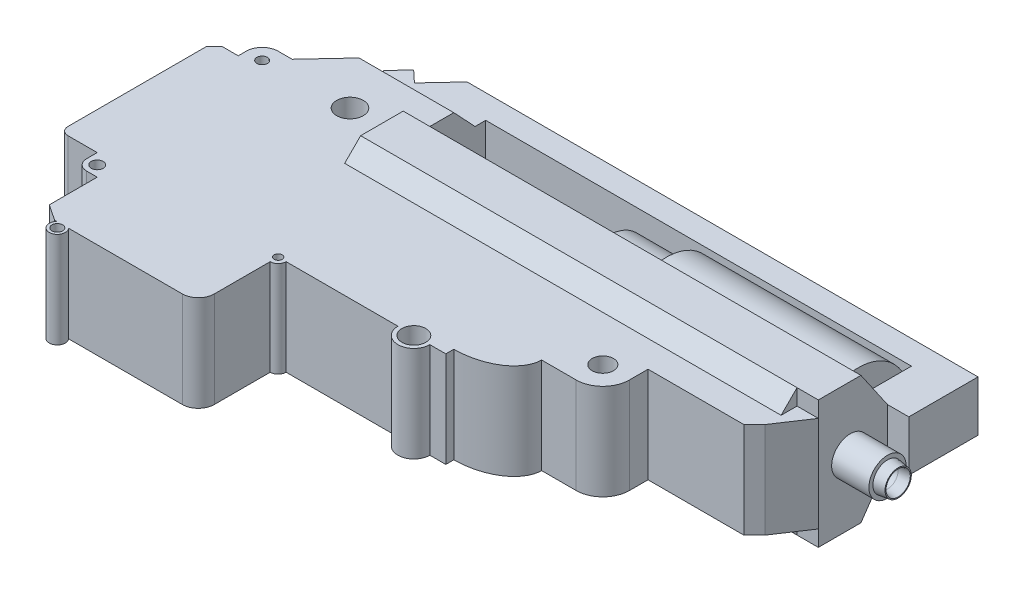
SolidWorks part; units mm, degrees
ref_plane "Alzado" through (0, 0, 0) normal (0, 0, 1) x (1, 0, 0)
ref_plane "Planta" through (0, 0, 0) normal (0, 1, 0) x (1, 0, 0)
ref_plane "Vista lateral" through (0, 0, 0) normal (1, 0, 0) x (0, 0, -1)
sketch "Croquis1" plane through (0, 0, 0) normal (0, 1, 0) x (1, 0, 0)
  line L0 (0, 0) -> (96, 0)
  line L1 (96, 0) -> (96, -13)
  line L2 (0, 0) -> (-4.2707, -4.5758)
  line L3 (96, -13) -> (88, -13)
  line L4 (96, -13) -> (96, -10.5)
  line L6 (88, -4.5) -> (88, -13)
  line L7 (88, -4.5) -> (8, -4.5)
  line L8 (88, -13) -> (87.902, -13.0151)
  line L9 (8, -4.5) -> (8, -7.5)
  line L10 (8, -7.5) -> (-7, -7.5)
  line L11 (-7, -7.5) -> (-9.9242, -4.7707)
  line L12 (-9.9242, -4.7707) -> (-7.1949, -1.8465)
  line L13 (-7.1949, -1.8465) -> (-4.2707, -4.5758)
  line L14 (-7, -7.5) -> (-10.4116, -11.1553) construction
  line L15 (-13.3358, -8.426) -> (-10.4116, -11.1553)
  line L16 (-13.1409, -14.0795) -> (-16.0651, -11.3502)
  line L17 (-16.0651, -11.3502) -> (-13.3358, -8.426)
  line L18 (-13.1409, -14.0795) -> (-10.4116, -11.1553)
  dimension "D1" = 96
  dimension "D2" = 13
  dimension "D3" = 15
  dimension "D4" = 8
  dimension "D8" = 80
  dimension "D9" = 4
  dimension "D10" = 4
  dimension "D11" = 5
extrude "Saliente-Extruir1" add sketch "Croquis1" along normal blind 9.5 contours L1 L0 L2 L10 L9 L7 L6 L3 | L16 L18 L15 L17 region at (47.5288, 0, 3.3855) region at (-13.2383, 0, 11.2528)
sketch "Croquis2" plane through (88, 0, 0) normal (-1, 0, 0) x (0, 0, 1)
  line L0 (4.5, 4.75) -> (5, 4.75) construction
  line L2 (4.5, 9.5) -> (4.5, 0) construction
  line L3 (5, 4.75) -> (14.5, 4.75) construction
  circle A0 centre (14.5, 4.75) radius 9.5
  dimension "D1" = 0.5
  dimension "D2" = 9.5
extrude "Saliente-Extruir2" add sketch "Croquis2" along normal blind 36
sketch "Croquis3" plane through (52, 0, 0) normal (-1, 0, 0) x (0, 0, 1)
  circle A0 centre (14.5, 4.75) radius 7.5
  dimension "D1" = 15
extrude "Saliente-Extruir3" add sketch "Croquis3" along normal blind 11
sketch "Croquis5" plane through (41, 0, 0) normal (-1, 0, 0) x (0, 0, 1)
  circle A0 centre (14.5, 4.75) radius 3.5
  dimension "D1" = 7
extrude "Saliente-Extruir4" add sketch "Croquis5" along normal blind 33
sketch "Croquis6" plane through (88, 0, 0) normal (1, 0, 0) x (0, 0, -1)
  line L0 (-13, 4.75) -> (-26, 4.75) construction
  line L1 (-13, 9.5) -> (-13, 0) construction
  line L2 (-26, -7.25) -> (-26, 16.75)
  line L3 (-26, 16.75) -> (-18, 16.75)
  line L4 (-18, 16.75) -> (-13, 9.5)
  line L5 (-13, 9.5) -> (-13, 0)
  line L6 (-18, -7.25) -> (-13, 0)
  line L7 (-26, -7.25) -> (-18, -7.25)
  dimension "D1" = 13
  dimension "D2" = 12
  dimension "D3" = 8
extrude "Saliente-Extruir5" add sketch "Croquis6" along normal blind 4
sketch "Croquis7" plane through (92, 0, 0) normal (1, 0, 0) x (0, 0, -1)
  line L0 (-13, 4.75) -> (-20, 4.75) construction
  line L1 (-13, 0) -> (-13, 9.5) construction
  circle A0 centre (-20, 4.75) radius 3.5
  circle A1 centre (-20, 4.75) radius 2
  dimension "D2" = 7
  dimension "D3" = 4
  dimension "D1" = 7
extrude "Saliente-Extruir6" add sketch "Croquis7" along normal blind 7
sketch "Croquis8" plane through (99, 0, 0) normal (1, 0, 0) x (0, 0, -1)
  circle A0 centre (-20, 4.75) radius 2
  circle A1 centre (-20, 4.75) radius 2.75
  dimension "D1" = 5.5
extrude "Saliente-Extruir7" add sketch "Croquis8" along normal blind 2 draft 8
sketch "Croquis9" plane through (8, 0, 0) normal (-1, 0, 0) x (0, 0, 1)
  line L10 (6.5, 9.5) -> (10.5, 13.75)
  line L13 (4.5, 4.75) -> (17.5, 4.75) construction
  line L14 (10.5, 13.75) -> (17.5, 13.75)
  line L15 (17.5, -4.25) -> (17.5, 13.75)
  line L18 (4.5, 0) -> (4.5, 9.5)
  line L19 (4.5, 0) -> (6.5, 0)
  line L20 (4.5, 9.5) -> (10.5, 9.5) construction
  line L21 (17.5, -4.25) -> (10.5, -4.25)
  line L22 (4.5, 9.5) -> (6.5, 9.5)
  line L23 (10.5, 9.5) -> (10.5, 13.75) construction
  line L24 (6.5, 0) -> (10.5, -4.25)
  dimension "D3" = 13
  dimension "D6" = 2
  dimension "D7" = 6
extrude "Saliente-Extruir8" add sketch "Croquis9" along normal blind 23
sketch "Croquis17" plane through (0, 13.75, 0) normal (0, 1, 0) x (1, 0, 0)
  line L0 (0, 0) -> (-16.8, -18)
  line L1 (-16.8, -18) -> (-16.7852, -17.9144)
  line L4 (0, 0) -> (-16.8, 0)
  line L5 (-16.8, 0) -> (-16.8, -18)
  line M3 (8, -10.5) -> (-15, -10.5)
  line M4 (-15, -10.5) -> (-15, -17.5)
extrude "Cortar-Extruir3" cut sketch "Croquis17" along normal blind 40 and the other way blind 34 contours L4 L5 L0 M4 M3 | L0 M3 M4 region at (-10.981, 13.75, 5.3264) region at (-13.2667, 13.75, 12.3571)
sketch "Croquis18" plane through (88, 0, 0) normal (-1, 0, 0) x (0, 0, 1)
  line L0 (18, -7.25) -> (26, -7.25)
  line L1 (26, 16.75) -> (26, -7.25) construction
  line L2 (26, 16.75) -> (18, 16.75)
  line L3 (18, 16.75) -> (18, 13.75)
  line L4 (18, 13.75) -> (26, 13.75)
  line L5 (26, 13.75) -> (29, 13.75)
  line L6 (26, 16.75) -> (29, 13.75)
  line L7 (26, -4.25) -> (29, -4.25)
  line L8 (18, -7.25) -> (18, -4.25)
  line L9 (18, -4.25) -> (26, -4.25)
  line L10 (29, -4.25) -> (26, -7.25)
  dimension "D1" = 3
  dimension "D2" = 3
extrude "Saliente-Extruir10" add sketch "Croquis18" along normal blind 82
sketch "Croquis19" plane through (0, 13.75, 0) normal (0, 1, 0) x (1, 0, 0)
  line L0 (8, -17.5) -> (8, -24.5)
  line L1 (8, -24.5) -> (-26, -24.5)
  line L2 (-26, -24.5) -> (-26, -23)
  line L3 (-26, -23) -> (-24.5, -23) construction
  line L4 (-24.5, -23) -> (-24.5, -21.5) construction
  line L5 (-26, -23) -> (-24.5, -21.5)
  line L6 (-24.5, -21.5) -> (-21.5, -21.5)
  line L7 (-21.5, -21.5) -> (-18.5, -21.5) construction
  line L8 (-18.5, -21.5) -> (-18.5, -20) construction
  line L9 (-18.5, -20) -> (-18.5, -17) construction
  line L10 (-18.5, -17) -> (-16.8667, -17)
  line L11 (8, -17.5) -> (-15, -17.5)
  line L12 (-15, -16.0714) -> (-15.8667, -17)
  line L13 (-15, -16.0714) -> (-15, -17.5)
  line L14 (-21.5, -21.5) -> (-21.5, -20)
  line L15 (-16.8667, -17) -> (-15.8667, -17)
  line L16 (0, 0) -> (0, -19.5) construction
  line L17 (0, -19.5) -> (-2.5, -19.5) construction
  line L20 (-9.8, -10.5) -> (-15, -16.0714)
  line L21 (-15, -16.0714) -> (-15, -17.5)
  line L22 (-15, -17.5) -> (8, -17.5)
  line L23 (8, -17.5) -> (8, -10.5)
  line L24 (8, -10.5) -> (-9.8, -10.5)
  line L25 (-9.8, -10.5) -> (-12.4, -13.2857)
  line L27 (-15, -17.5) -> (8, -17.5)
  line L28 (8, -17.5) -> (8, -10.5)
  line L29 (8, -10.5) -> (-9.8, -10.5)
  arc A0 (-18.5, -17) -> (-21.5, -20) centre (-18.5, -20) ccw
  circle A1 centre (-18.5, -20) radius 1
  line M11 (-15, -16.0714) -> (-15, -17.5)
  line M12 (-15, -17.5) -> (8, -17.5)
  dimension "D11" = 2
  dimension "D1" = 7
  dimension "D2" = 34
  dimension "D3" = 1.5
  dimension "D4" = 1.5
  dimension "D5" = 1.5
  dimension "D6" = 3
  dimension "D7" = 3
  dimension "D8" = 1.5
  dimension "D9" = 3
  dimension "D12" = 19.5
  dimension "D13" = 2.5
  dimension "D10" = 0
extrude "Saliente-Extruir11" add sketch "Croquis19" against normal blind 18 contours L10 A0 L14 L6 L5 L2 L1 L0 M12 M11 region at (-7.6013, 13.75, 21.099)
sketch "Croquis20" plane through (0, 13.75, 0) normal (0, 1, 0) x (1, 0, 0)
  line L0 (0, 0) -> (0, -19.5) construction
  line L1 (0, -19.5) -> (-2.5, -19.5) construction
  circle A0 centre (-2.5, -19.5) radius 2.5
  dimension "D1" = 19.5
  dimension "D2" = 2.5
extrude "Cortar-Extruir4" cut sketch "Croquis20" against normal blind 18
sketch "Croquis21" plane through (0, 13.75, 0) normal (0, 1, 0) x (1, 0, 0)
  line L0 (-26, -24.5) -> (-26, -49)
  line L1 (-24.5, -50.5) -> (-19, -50.5)
  line L2 (-26, -24.5) -> (6, -24.5)
  line L4 (-19, -50.5) -> (-19, -52.5)
  line L5 (-15, -54.5) -> (-15, -63.5)
  line L6 (-15, -63.5) -> (-12, -63.5) construction
  line L7 (-12, -63.5) -> (-12, -65.5) construction
  line L8 (-15, -63.5) -> (-12, -65.5)
  line L9 (-12, -65.5) -> (-11.618, -65.5)
  line L10 (-12, -65.5) -> (-11.618, -65.5)
  line L11 (15, -62.5) -> (15, -52)
  line L12 (-9.382, -65.5) -> (12, -65.5)
  line L14 (16.5, -50.5) -> (37.5, -50.5)
  line L15 (43.5, -50.5) -> (46.5, -50.5)
  line L16 (46.5, -50.5) -> (46.5, -49)
  line L19 (92, -26) -> (88, -32)
  line L20 (88, -32) -> (86, -32) construction
  line L21 (86, -32) -> (86, -34) construction
  line L22 (88, -32) -> (86, -34)
  line L23 (86, -34) -> (68, -34)
  line L24 (96, 0) -> (96, -37.5) construction
  line L25 (-17, -54.5) -> (-15, -54.5)
  line L26 (96, -37.5) -> (63, -37.5) construction
  line L27 (68, -34) -> (68, -37.5)
  line L28 (63, 0) -> (63, -40) construction
  line L29 (0, 0) -> (96, 0) construction
  line L30 (63, -42.5) -> (56.5, -42.5)
  line L31 (6, -24.5) -> (92, -24.5)
  line L32 (92, -18) -> (92, -26) construction
  line L33 (92, -24.5) -> (92, -26)
  arc A0 (-19, -52.5) -> (-17, -54.5) centre (-17, -52.5) ccw
  arc A1 (-11.618, -65.5) -> (-9.382, -65.5) centre (-10.5, -66.5) ccw
  arc A2 (12, -65.5) -> (15, -62.5) centre (12, -62.5) ccw
  arc A3 (15, -52) -> (16.5, -50.5) centre (15, -50.5) ccw
  arc A4 (37.5, -50.5) -> (43.5, -50.5) centre (40.5, -50.5) ccw
  circle A5 centre (63, -37.5) radius 2
  arc A6 (63, -42.5) -> (68, -37.5) centre (63, -37.5) ccw
  circle A7 centre (-10.5, -66.5) radius 0.9991
  circle A8 centre (40.5, -50.5) radius 2.25
  circle A9 centre (15, -50.5) radius 0.75
  circle A10 centre (-17, -52.5) radius 1.1246
  arc A11 (-24.5, -50.5) -> (-26, -49) centre (-24.5, -49) cw
  ellipse E0 centre (46.5, -42.5) end of major axis (56.5, -42.5) minor radius 6.5 (46.5, -49) -> (56.5, -42.5) ccw
  point P57 (-26, -50.5)
  line M13 (-26, -24.5) -> (6, -24.5)
  dimension "D5" = 4
  dimension "D12" = 3
  dimension "D11" = 3
  dimension "D23" = 4
  dimension "D3" = 4.5
  dimension "D4" = 1.5
  dimension "D6" = 1.5
  dimension "D1" = 26
  dimension "D2" = 7
  dimension "D7" = 3
  dimension "D8" = 2
  dimension "D9" = 24
  dimension "D10" = 12
  dimension "D13" = 21
  dimension "D14" = 6
  dimension "D15" = 3
  dimension "D16" = 1.5
  dimension "D18" = 2
  dimension "D19" = 2
  dimension "D20" = 18
  dimension "D21" = 37.5
  dimension "D22" = 33
  dimension "D24" = 40
  dimension "D25" = 6.5
extrude "Saliente-Extruir19" add sketch "Croquis21" against normal blind 18 contours L16 E0 L30 A6 L27 L23 L22 L19 L33 L31 L0 L1 L4 A0 L25 L5 L8 L9 A1 L12 A2 L11 A3 L14 A4 L15 A5 M13 region at (19.8463, 13.75, 39.6627)
sketch "Croquis22" plane through (0, 9.5, 0) normal (0, 1, 0) x (1, 0, 0)
  line L0 (0, 0) -> (-4.7762, -5.1174) construction
  line L1 (0, 0) -> (-6.0667, -6.5) construction
  line L2 (-4.7762, -5.1174) -> (-6.9694, -3.0704)
  line L3 (-4.7762, -5.1174) -> (-7.5055, -8.0416)
  line L4 (-9.8, -10.5) -> (-6.0667, -6.5) construction
  line L5 (-7.5055, -8.0416) -> (-9.6987, -5.9947)
  line L6 (-9.6987, -5.9947) -> (-6.9694, -3.0704)
  line L7 (-7.5055, -8.0416) -> (-10.2348, -10.9658) construction
  line L8 (-15.8667, -17) -> (-9.8, -10.5) construction
  line L9 (-10.2348, -10.9658) -> (-12.4279, -8.9189)
  line L10 (-12.4279, -8.9189) -> (-15.1572, -11.8431)
  line L11 (-15.1572, -11.8431) -> (-12.964, -13.8901)
  line L12 (-10.2348, -10.9658) -> (-12.964, -13.8901)
  dimension "D1" = 7
  dimension "D2" = 3
  dimension "D3" = 4
  dimension "D4" = 3
  dimension "D5" = 4
  dimension "D6" = 4
extrude "Saliente-Extruir20" add sketch "Croquis22" against normal blind 9.5
